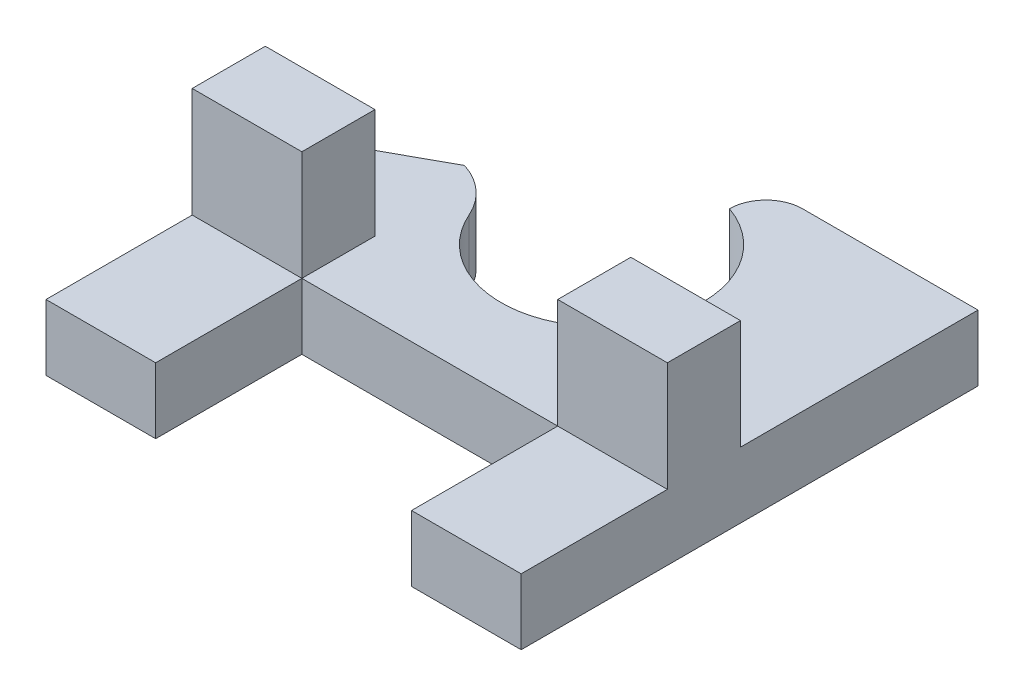
SolidWorks part; units mm, degrees
ref_plane "Front Plane" through (0, 0, 0) normal (0, 0, 1) x (1, 0, 0)
ref_plane "Top Plane" through (0, 0, 0) normal (0, 1, 0) x (1, 0, 0)
ref_plane "Right Plane" through (0, 0, 0) normal (1, 0, 0) x (0, 0, -1)
sketch "Sketch1" plane through (0, 0, 0) normal (0, 1, 0) x (1, 0, 0)
  line L0 (6.5, 2.5) -> (6.5, 0)
  line L1 (3.5, 0) -> (-3.5, 0)
  line L2 (-6.5, 0) -> (-6.5, 2.5)
  line L5 (-6.5, 2.5) -> (-6.5, 3.5)
  line L7 (6.5, 0) -> (6.5, -4)
  line L8 (6.5, -4) -> (3.5, -4)
  line L9 (3.5, 0) -> (3.5, -4)
  line L11 (-6.5, 0) -> (-6.5, -4)
  line L12 (-6.5, -4) -> (-3.5, -4)
  line L13 (-3.5, 0) -> (-3.5, -4)
  line L15 (6.5, 4.9) -> (6.5, 2.5)
  line L17 (-2.95, 4.9) -> (-3.95, 4.9)
  line L18 (-3.95, 4.9) -> (-6.5, 3.5)
  line L19 (0.7, 7.4986) -> (0.7, 8.4986)
  line L20 (0.7, 8.4986) -> (6.5, 8.4986)
  line L21 (6.5, 8.4986) -> (6.5, 4.9)
  arc A2 (-2.95, 4.9) -> (2.55, 4.9) centre (-0.2, 4.9) ccw
  arc A3 (2.55, 4.9) -> (0.7, 7.4986) centre (-0.2, 4.9) ccw
  point P0 (0, 0)
  dimension "D1" = 2.4
  dimension "D2" = 5.5
  dimension "D3" = 13
  dimension "D4" = 6.3
  dimension "D5" = 2.5
  dimension "D6" = 1
  dimension "D7" = 1
  dimension "D8" = 4
  dimension "D9" = 3
  dimension "D11" = 2.4
  dimension "D12" = 1
  dimension "D13" = 5.8
extrude "Boss-Extrude1" add sketch "Sketch1" along normal blind 1.8
fillet "Fillet1" radius 2 1 edges at (-2.95, 0.9, -4.9)
fillet "Fillet3" radius 1 1 edges at (0.7, 0.9, -8.4986)
ref_plane "Plane1" through (0, 0, 0) normal (0, -1, 0) x (-1, 0, 0)
sketch "Sketch2" plane through (0, 0, 0) normal (0, -1, 0) x (1, 0, 0)
  line L0 (6.5, 4) -> (6.5, -8.4986) construction
  line L1 (3.5, 0) -> (6.5, 0)
  line L2 (3.5, 0) -> (3.5, -2)
  line L3 (3.5, -2) -> (6.5, -2)
  line L4 (6.5, 0) -> (6.5, -2)
  line L5 (-6.5, -3.5) -> (-6.5, 4) construction
  line L6 (-3.5, 0) -> (-6.5, 0)
  line L7 (-3.5, 0) -> (-3.5, -2)
  line L8 (-3.5, -2) -> (-6.5, -2)
  line L9 (-6.5, 0) -> (-6.5, -2)
  dimension "D1" = 2
extrude "Boss-Extrude2" add sketch "Sketch2" along normal blind 3
mirror "Mirror3" about plane through (0, 0, 0) normal (0, -1, 0) of bodies 104
delete or keep bodies "Body-Delete/Keep 1" type delete bodies bodies 104
